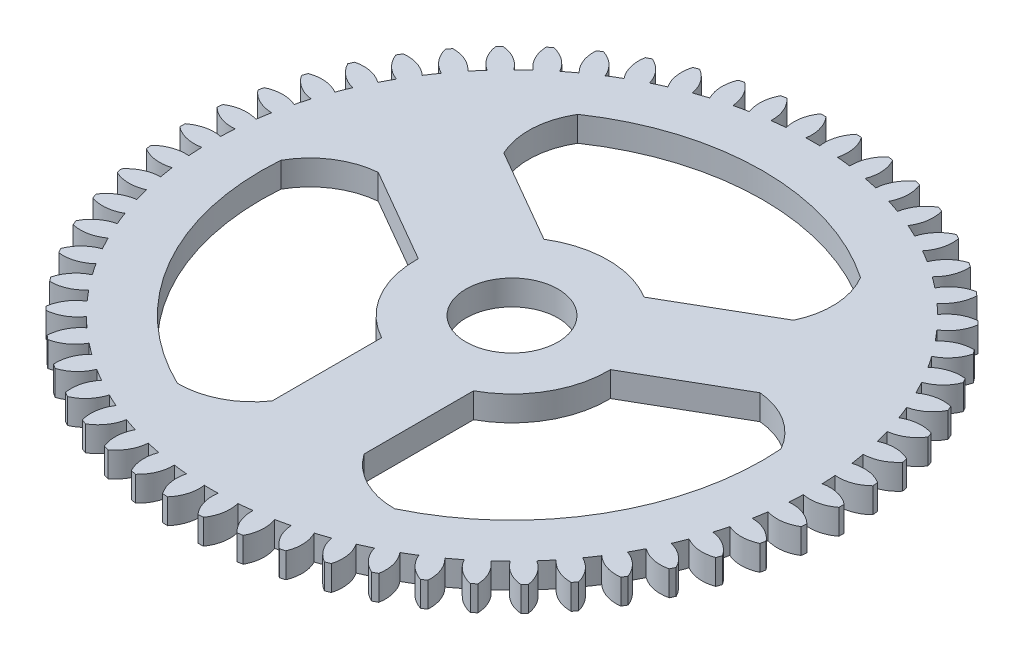
SolidWorks part; units mm, degrees
ref_plane "Front Plane" through (0, 0, 0) normal (0, 0, 1) x (1, 0, 0)
ref_plane "Top Plane" through (0, 0, 0) normal (0, 1, 0) x (1, 0, 0)
ref_plane "Right Plane" through (0, 0, 0) normal (1, 0, 0) x (0, 0, -1)
sketch "Sketch1" plane through (0, 0, 0) normal (0, 1, 0) x (1, 0, 0)
  line L0 (0, -72) -> (0, 72) construction
  line L1 (-72, 0) -> (72, 0) construction
  line L2 (50.9117, -50.9117) -> (-50.9117, 50.9117) construction
  line L3 (-50.9117, -50.9117) -> (50.9117, 50.9117) construction
  circle A58 centre (0, 0) radius 72
  arc A59 (-71.9648, 2.2507) -> (-78.8549, 0.6353) centre (-73.6708, -5.9742) ccw
  arc A60 (-78.8549, 0.6353) -> (-78.8549, -0.6353) centre (390.4055, 0) ccw
  arc A61 (-78.8549, -0.6353) -> (-71.9648, -2.2507) centre (-73.6708, 5.9742) ccw
  arc A62 (-71.9648, 2.2507) -> (-71.9648, -2.2507) centre (0, 0) ccw
  arc A63 (-71.2996, 10.0183) -> (-78.3239, 9.1572) centre (-73.8848, 2.026) ccw
  arc A64 (-78.3239, 9.1572) -> (-78.4613, 7.8942) centre (388.117, -42.2103) ccw
  arc A65 (-78.4613, 7.8942) -> (-71.7863, 5.5432) centre (-72.593, 13.9044) ccw
  arc A66 (-69.7985, 17.6684) -> (-76.8747, 17.5719) centre (-73.2327, 10.0025) ccw
  arc A67 (-76.8747, 17.5719) -> (-77.1479, 16.3311) centre (381.2781, -83.9257) ccw
  arc A68 (-77.1479, 16.3311) -> (-70.7662, 13.2722) centre (-70.6641, 21.6716) ccw
  arc A69 (-67.479, 25.1114) -> (-74.5242, 25.7805) centre (-71.7219, 17.8617) ccw
  arc A70 (-74.5242, 25.7805) -> (-74.9299, 24.5765) centre (369.9691, -124.6571) ccw
  arc A71 (-74.9299, 24.5765) -> (-68.9163, 20.8456) centre (-67.9068, 29.1847) ccw
  arc A72 (-64.3684, 32.2599) -> (-71.3, 33.6868) centre (-69.3703, 25.5115) ccw
  arc A73 (-71.3, 33.6868) -> (-71.8335, 32.5338) centre (354.3225, -163.927) ccw
  arc A74 (-71.8335, 32.5338) -> (-66.2586, 28.1745) centre (-64.3533, 36.3556) ccw
  arc A75 (-60.5032, 39.0303) -> (-67.2399, 41.1983) centre (-66.2054, 32.8622) ccw
  arc A76 (-67.2399, 41.1983) -> (-67.8949, 40.1096) centre (334.5218, -201.2751) ccw
  arc A77 (-67.8949, 40.1096) -> (-62.8239, 35.1732) centre (-60.0453, 43.1003) ccw
  arc A78 (-55.9286, 45.343) -> (-62.3914, 48.2267) centre (-62.2642, 39.8276) ccw
  arc A79 (-62.3914, 48.2267) -> (-63.1603, 47.2152) centre (310.7991, -236.2634) ccw
  arc A80 (-63.1603, 47.2152) -> (-58.6528, 41.7595) centre (-55.0333, 49.3397) ccw
  arc A81 (-50.6983, 51.1242) -> (-56.8114, 54.6896) centre (-57.5931, 46.3261) ccw
  arc A82 (-56.8114, 54.6896) -> (-57.6851, 53.7673) centre (283.4327, -268.4817) ccw
  arc A83 (-57.6851, 53.7673) -> (-53.794, 47.8561) centre (-49.3762, 55.0006) ccw
  arc A84 (-44.8736, 56.3059) -> (-50.5654, 60.5114) centre (-52.2468, 52.2814) ccw
  arc A85 (-50.5654, 60.5114) -> (-51.5337, 59.6889) centre (252.7432, -297.5523) ccw
  arc A86 (-51.5337, 59.6889) -> (-48.3045, 53.3918) centre (-43.1401, 60.0167) ccw
  arc A87 (-38.5228, 60.8276) -> (-43.7265, 65.6238) centre (-46.2879, 57.6238) ccw
  arc A88 (-43.7265, 65.6238) -> (-44.7781, 64.9108) centre (219.0905, -323.1344) ccw
  arc A89 (-44.7781, 64.9108) -> (-42.2486, 58.3014) centre (-36.3983, 64.3291) ccw
  arc A90 (-31.7204, 64.636) -> (-36.375, 69.9668) centre (-39.7863, 62.2906) ccw
  arc A91 (-36.375, 69.9668) -> (-37.4975, 69.3717) centre (182.8693, -344.928) ccw
  arc A92 (-37.4975, 69.3717) -> (-35.6975, 62.5275) centre (-29.2297, 67.8874) ccw
  arc A93 (-24.546, 67.6867) -> (-28.5971, 73.4895) centre (-32.8183, 66.2271) ccw
  arc A94 (-28.5971, 73.4895) -> (-29.7773, 73.0192) centre (144.504, -362.6777) ccw
  arc A95 (-29.7773, 73.0192) -> (-28.7278, 66.0206) centre (-21.7185, 70.6497) ccw
  arc A96 (-17.0839, 69.9438) -> (-20.4838, 76.1506) centre (-25.4655, 69.3872) ccw
  arc A97 (-20.4838, 76.1506) -> (-21.708, 75.8107) centre (104.4445, -376.1753) ccw
  arc A98 (-21.708, 75.8107) -> (-21.4213, 68.7396) centre (-13.9526, 72.5837) ccw
  arc A99 (-9.4215, 71.3809) -> (-12.1304, 77.9189) centre (-17.8141, 71.7338) ccw
  arc A100 (-12.1304, 77.9189) -> (-13.3842, 77.7133) centre (63.1606, -385.2625) ccw
  arc A101 (-13.3842, 77.7133) -> (-13.8637, 70.6527) centre (-6.0231, 73.6668) ccw
  arc A102 (-1.6487, 71.9811) -> (-3.6348, 78.7736) centre (-9.9539, 73.2393) ccw
  arc A103 (-3.6348, 78.7736) -> (-4.9034, 78.7048) centre (21.1361, -389.833) ccw
  arc A104 (-4.9034, 78.7048) -> (-6.1435, 71.7374) centre (1.977, 73.8862) ccw
  arc A105 (6.1435, 71.7374) -> (4.9034, 78.7048) centre (-1.977, 73.8862) ccw
  arc A106 (4.9034, 78.7048) -> (3.6348, 78.7736) centre (-21.1361, -389.833) ccw
  arc A107 (3.6348, 78.7736) -> (1.6487, 71.9811) centre (9.9539, 73.2393) ccw
  arc A108 (13.8637, 70.6527) -> (13.3842, 77.7133) centre (6.0231, 73.6668) ccw
  arc A109 (13.3842, 77.7133) -> (12.1304, 77.9189) centre (-63.1606, -385.2625) ccw
  arc A110 (12.1304, 77.9189) -> (9.4215, 71.3809) centre (17.8141, 71.7338) ccw
  arc A111 (21.4213, 68.7396) -> (21.708, 75.8107) centre (13.9526, 72.5837) ccw
  arc A112 (21.708, 75.8107) -> (20.4838, 76.1506) centre (-104.4445, -376.1753) ccw
  arc A113 (20.4838, 76.1506) -> (17.0839, 69.9438) centre (25.4655, 69.3872) ccw
  arc A114 (28.7278, 66.0206) -> (29.7773, 73.0192) centre (21.7185, 70.6497) ccw
  arc A115 (29.7773, 73.0192) -> (28.5971, 73.4895) centre (-144.504, -362.6777) ccw
  arc A116 (28.5971, 73.4895) -> (24.546, 67.6867) centre (32.8183, 66.2271) ccw
  arc A117 (35.6975, 62.5275) -> (37.4975, 69.3717) centre (29.2297, 67.8874) ccw
  arc A118 (37.4975, 69.3717) -> (36.375, 69.9668) centre (-182.8693, -344.928) ccw
  arc A119 (36.375, 69.9668) -> (31.7204, 64.636) centre (39.7863, 62.2906) ccw
  arc A120 (42.2486, 58.3014) -> (44.7781, 64.9108) centre (36.3983, 64.3291) ccw
  arc A121 (44.7781, 64.9108) -> (43.7265, 65.6238) centre (-219.0905, -323.1344) ccw
  arc A122 (43.7265, 65.6238) -> (38.5228, 60.8276) centre (46.2879, 57.6238) ccw
  arc A123 (48.3045, 53.3918) -> (51.5337, 59.6889) centre (43.1401, 60.0167) ccw
  arc A124 (51.5337, 59.6889) -> (50.5654, 60.5114) centre (-252.7432, -297.5523) ccw
  arc A125 (50.5654, 60.5114) -> (44.8736, 56.3059) centre (52.2468, 52.2814) ccw
  arc A126 (53.794, 47.8561) -> (57.6851, 53.7673) centre (49.3762, 55.0006) ccw
  arc A127 (57.6851, 53.7673) -> (56.8114, 54.6896) centre (-283.4327, -268.4817) ccw
  arc A128 (56.8114, 54.6896) -> (50.6983, 51.1242) centre (57.5931, 46.3261) ccw
  arc A129 (58.6528, 41.7595) -> (63.1603, 47.2152) centre (55.0333, 49.3397) ccw
  arc A130 (63.1603, 47.2152) -> (62.3914, 48.2267) centre (-310.7991, -236.2634) ccw
  arc A131 (62.3914, 48.2267) -> (55.9286, 45.343) centre (62.2642, 39.8276) ccw
  arc A132 (62.8239, 35.1732) -> (67.8949, 40.1096) centre (60.0453, 43.1003) ccw
  arc A133 (67.8949, 40.1096) -> (67.2399, 41.1983) centre (-334.5218, -201.2751) ccw
  arc A134 (67.2399, 41.1983) -> (60.5032, 39.0303) centre (66.2054, 32.8622) ccw
  arc A135 (66.2586, 28.1745) -> (71.8335, 32.5338) centre (64.3533, 36.3556) ccw
  arc A136 (71.8335, 32.5338) -> (71.3, 33.6868) centre (-354.3225, -163.927) ccw
  arc A137 (71.3, 33.6868) -> (64.3684, 32.2599) centre (69.3703, 25.5115) ccw
  arc A138 (68.9163, 20.8456) -> (74.9299, 24.5765) centre (67.9068, 29.1847) ccw
  arc A139 (74.9299, 24.5765) -> (74.5242, 25.7805) centre (-369.9691, -124.6571) ccw
  arc A140 (74.5242, 25.7805) -> (67.479, 25.1114) centre (71.7219, 17.8617) ccw
  arc A141 (70.7662, 13.2722) -> (77.1479, 16.3311) centre (70.6641, 21.6716) ccw
  arc A142 (77.1479, 16.3311) -> (76.8747, 17.5719) centre (-381.2781, -83.9257) ccw
  arc A143 (76.8747, 17.5719) -> (69.7985, 17.6684) centre (73.2327, 10.0025) ccw
  arc A144 (71.7863, 5.5432) -> (78.4613, 7.8942) centre (72.593, 13.9044) ccw
  arc A145 (78.4613, 7.8942) -> (78.3239, 9.1572) centre (-388.117, -42.2103) ccw
  arc A146 (78.3239, 9.1572) -> (71.2996, 10.0183) centre (73.8848, 2.026) ccw
  arc A147 (71.9648, -2.2507) -> (78.8549, -0.6353) centre (73.6708, 5.9742) ccw
  arc A148 (78.8549, -0.6353) -> (78.8549, 0.6353) centre (-390.4055, 0) ccw
  arc A149 (78.8549, 0.6353) -> (71.9648, 2.2507) centre (73.6708, -5.9742) ccw
  arc A150 (71.2996, -10.0183) -> (78.3239, -9.1572) centre (73.8848, -2.026) ccw
  arc A151 (78.3239, -9.1572) -> (78.4613, -7.8942) centre (-388.117, 42.2103) ccw
  arc A152 (78.4613, -7.8942) -> (71.7863, -5.5432) centre (72.593, -13.9044) ccw
  arc A153 (69.7985, -17.6684) -> (76.8747, -17.5719) centre (73.2327, -10.0025) ccw
  arc A154 (76.8747, -17.5719) -> (77.1479, -16.3311) centre (-381.2781, 83.9257) ccw
  arc A155 (77.1479, -16.3311) -> (70.7662, -13.2722) centre (70.6641, -21.6716) ccw
  arc A156 (67.479, -25.1114) -> (74.5242, -25.7805) centre (71.7219, -17.8617) ccw
  arc A157 (74.5242, -25.7805) -> (74.9299, -24.5765) centre (-369.9691, 124.6571) ccw
  arc A158 (74.9299, -24.5765) -> (68.9163, -20.8456) centre (67.9068, -29.1847) ccw
  arc A159 (64.3684, -32.2599) -> (71.3, -33.6868) centre (69.3703, -25.5115) ccw
  arc A160 (71.3, -33.6868) -> (71.8335, -32.5338) centre (-354.3225, 163.927) ccw
  arc A161 (71.8335, -32.5338) -> (66.2586, -28.1745) centre (64.3533, -36.3556) ccw
  arc A162 (60.5032, -39.0303) -> (67.2399, -41.1983) centre (66.2054, -32.8622) ccw
  arc A163 (67.2399, -41.1983) -> (67.8949, -40.1096) centre (-334.5218, 201.2751) ccw
  arc A164 (67.8949, -40.1096) -> (62.8239, -35.1732) centre (60.0453, -43.1003) ccw
  arc A165 (55.9286, -45.343) -> (62.3914, -48.2267) centre (62.2642, -39.8276) ccw
  arc A166 (62.3914, -48.2267) -> (63.1603, -47.2152) centre (-310.7991, 236.2634) ccw
  arc A167 (63.1603, -47.2152) -> (58.6528, -41.7595) centre (55.0333, -49.3397) ccw
  arc A168 (50.6983, -51.1242) -> (56.8114, -54.6896) centre (57.5931, -46.3261) ccw
  arc A169 (56.8114, -54.6896) -> (57.6851, -53.7673) centre (-283.4327, 268.4817) ccw
  arc A170 (57.6851, -53.7673) -> (53.794, -47.8561) centre (49.3762, -55.0006) ccw
  arc A171 (44.8736, -56.3059) -> (50.5654, -60.5114) centre (52.2468, -52.2814) ccw
  arc A172 (50.5654, -60.5114) -> (51.5337, -59.6889) centre (-252.7432, 297.5523) ccw
  arc A173 (51.5337, -59.6889) -> (48.3045, -53.3918) centre (43.1401, -60.0167) ccw
  arc A174 (38.5228, -60.8276) -> (43.7265, -65.6238) centre (46.2879, -57.6238) ccw
  arc A175 (43.7265, -65.6238) -> (44.7781, -64.9108) centre (-219.0905, 323.1344) ccw
  arc A176 (44.7781, -64.9108) -> (42.2486, -58.3014) centre (36.3983, -64.3291) ccw
  arc A177 (31.7204, -64.636) -> (36.375, -69.9668) centre (39.7863, -62.2906) ccw
  arc A178 (36.375, -69.9668) -> (37.4975, -69.3717) centre (-182.8693, 344.928) ccw
  arc A179 (37.4975, -69.3717) -> (35.6975, -62.5275) centre (29.2297, -67.8874) ccw
  arc A180 (24.546, -67.6867) -> (28.5971, -73.4895) centre (32.8183, -66.2271) ccw
  arc A181 (28.5971, -73.4895) -> (29.7773, -73.0192) centre (-144.504, 362.6777) ccw
  arc A182 (29.7773, -73.0192) -> (28.7278, -66.0206) centre (21.7185, -70.6497) ccw
  arc A183 (17.0839, -69.9438) -> (20.4838, -76.1506) centre (25.4655, -69.3872) ccw
  arc A184 (20.4838, -76.1506) -> (21.708, -75.8107) centre (-104.4445, 376.1753) ccw
  arc A185 (21.708, -75.8107) -> (21.4213, -68.7396) centre (13.9526, -72.5837) ccw
  arc A186 (9.4215, -71.3809) -> (12.1304, -77.9189) centre (17.8141, -71.7338) ccw
  arc A187 (12.1304, -77.9189) -> (13.3842, -77.7133) centre (-63.1606, 385.2625) ccw
  arc A188 (13.3842, -77.7133) -> (13.8637, -70.6527) centre (6.0231, -73.6668) ccw
  arc A189 (1.6487, -71.9811) -> (3.6348, -78.7736) centre (9.9539, -73.2393) ccw
  arc A190 (3.6348, -78.7736) -> (4.9034, -78.7048) centre (-21.1361, 389.833) ccw
  arc A191 (4.9034, -78.7048) -> (6.1435, -71.7374) centre (-1.977, -73.8862) ccw
  arc A192 (-6.1435, -71.7374) -> (-4.9034, -78.7048) centre (1.977, -73.8862) ccw
  arc A193 (-4.9034, -78.7048) -> (-3.6348, -78.7736) centre (21.1361, 389.833) ccw
  arc A194 (-3.6348, -78.7736) -> (-1.6487, -71.9811) centre (-9.9539, -73.2393) ccw
  arc A195 (-13.8637, -70.6527) -> (-13.3842, -77.7133) centre (-6.0231, -73.6668) ccw
  arc A196 (-13.3842, -77.7133) -> (-12.1304, -77.9189) centre (63.1606, 385.2625) ccw
  arc A197 (-12.1304, -77.9189) -> (-9.4215, -71.3809) centre (-17.8141, -71.7338) ccw
  arc A198 (-21.4213, -68.7396) -> (-21.708, -75.8107) centre (-13.9526, -72.5837) ccw
  arc A199 (-21.708, -75.8107) -> (-20.4838, -76.1506) centre (104.4445, 376.1753) ccw
  arc A200 (-20.4838, -76.1506) -> (-17.0839, -69.9438) centre (-25.4655, -69.3872) ccw
  arc A201 (-28.7278, -66.0206) -> (-29.7773, -73.0192) centre (-21.7185, -70.6497) ccw
  arc A202 (-29.7773, -73.0192) -> (-28.5971, -73.4895) centre (144.504, 362.6777) ccw
  arc A203 (-28.5971, -73.4895) -> (-24.546, -67.6867) centre (-32.8183, -66.2271) ccw
  arc A204 (-35.6975, -62.5275) -> (-37.4975, -69.3717) centre (-29.2297, -67.8874) ccw
  arc A205 (-37.4975, -69.3717) -> (-36.375, -69.9668) centre (182.8693, 344.928) ccw
  arc A206 (-36.375, -69.9668) -> (-31.7204, -64.636) centre (-39.7863, -62.2906) ccw
  arc A207 (-42.2486, -58.3014) -> (-44.7781, -64.9108) centre (-36.3983, -64.3291) ccw
  arc A208 (-44.7781, -64.9108) -> (-43.7265, -65.6238) centre (219.0905, 323.1344) ccw
  arc A209 (-43.7265, -65.6238) -> (-38.5228, -60.8276) centre (-46.2879, -57.6238) ccw
  arc A210 (-48.3045, -53.3918) -> (-51.5337, -59.6889) centre (-43.1401, -60.0167) ccw
  arc A211 (-51.5337, -59.6889) -> (-50.5654, -60.5114) centre (252.7432, 297.5523) ccw
  arc A212 (-50.5654, -60.5114) -> (-44.8736, -56.3059) centre (-52.2468, -52.2814) ccw
  arc A213 (-53.794, -47.8561) -> (-57.6851, -53.7673) centre (-49.3762, -55.0006) ccw
  arc A214 (-57.6851, -53.7673) -> (-56.8114, -54.6896) centre (283.4327, 268.4817) ccw
  arc A215 (-56.8114, -54.6896) -> (-50.6983, -51.1242) centre (-57.5931, -46.3261) ccw
  arc A216 (-58.6528, -41.7595) -> (-63.1603, -47.2152) centre (-55.0333, -49.3397) ccw
  arc A217 (-63.1603, -47.2152) -> (-62.3914, -48.2267) centre (310.7991, 236.2634) ccw
  arc A218 (-62.3914, -48.2267) -> (-55.9286, -45.343) centre (-62.2642, -39.8276) ccw
  arc A219 (-62.8239, -35.1732) -> (-67.8949, -40.1096) centre (-60.0453, -43.1003) ccw
  arc A220 (-67.8949, -40.1096) -> (-67.2399, -41.1983) centre (334.5218, 201.2751) ccw
  arc A221 (-67.2399, -41.1983) -> (-60.5032, -39.0303) centre (-66.2054, -32.8622) ccw
  arc A222 (-66.2586, -28.1745) -> (-71.8335, -32.5338) centre (-64.3533, -36.3556) ccw
  arc A223 (-71.8335, -32.5338) -> (-71.3, -33.6868) centre (354.3225, 163.927) ccw
  arc A224 (-71.3, -33.6868) -> (-64.3684, -32.2599) centre (-69.3703, -25.5115) ccw
  arc A225 (-68.9163, -20.8456) -> (-74.9299, -24.5765) centre (-67.9068, -29.1847) ccw
  arc A226 (-74.9299, -24.5765) -> (-74.5242, -25.7805) centre (369.9691, 124.6571) ccw
  arc A227 (-74.5242, -25.7805) -> (-67.479, -25.1114) centre (-71.7219, -17.8617) ccw
  arc A228 (-70.7662, -13.2722) -> (-77.1479, -16.3311) centre (-70.6641, -21.6716) ccw
  arc A229 (-77.1479, -16.3311) -> (-76.8747, -17.5719) centre (381.2781, 83.9257) ccw
  arc A230 (-76.8747, -17.5719) -> (-69.7985, -17.6684) centre (-73.2327, -10.0025) ccw
  arc A231 (-71.7863, -5.5432) -> (-78.4613, -7.8942) centre (-72.593, -13.9044) ccw
  arc A232 (-78.4613, -7.8942) -> (-78.3239, -9.1572) centre (388.117, 42.2103) ccw
  arc A233 (-78.3239, -9.1572) -> (-71.2996, -10.0183) centre (-73.8848, -2.026) ccw
  circle A234 centre (0, 0) radius 11
  point P5 (0, 0)
  point P7 (0, 0)
  point P9 (-72, 0)
  point P10 (859.6664, 0)
  point P18 (0, 0)
  point P21 (0, 0)
  point P26 (0, 0)
  point P27 (0, 0)
  point P427 (0, 0)
  point P428 (0, 0)
  dimension "D1" = 144
  dimension "D2" = 45
  dimension "D3" = 45
  dimension "D4" = 8.4
  dimension "D5" = 1.2705
  dimension "D9" = 72
  dimension "D10" = 469.2609
  dimension "D12" = 22
  dimension "D6" = 6.8901
  dimension "D7" = 6.8901
  dimension "D8" = 4.5015
  dimension "D11" = 58
extrude "Boss-Extrude5" add sketch "Sketch1" along normal blind 6 contours A58 region at (69.955, 0, 1.0937)
extrude "Boss-Extrude6" add sketch "Sketch1<10>" along normal blind 6 contours A60 A61 A58 A59 region at (-74.9733, 0, 0)
sketch "Sketch1<10>" plane through (0, 0, 0) normal (0, 1, 0) x (1, 0, 0) same geometry as "Sketch1"
pattern_circular "CirPattern1" count 58 over 360 about axis through (0, 6, 0) along (0, 1, 0) of "Boss-Extrude6"
sketch "Sketch3" plane through (0, 6, 0) normal (0, 1, 0) x (1, 0, 0)
  line L1 (11.9929, 19.6258) -> (34.6743, 32.721)
  line L2 (0, -11) -> (0, -60) construction
  line L4 (-22.9929, 0.5732) -> (-45.6743, 13.6684)
  line L5 (-11, -20.199) -> (-11, -46.3893)
  line L6 (-11.9929, 19.6258) -> (-34.6743, 32.721)
  line L7 (22.9929, 0.5732) -> (45.6743, 13.6684)
  line L8 (11, -20.199) -> (11, -46.3893)
  arc A0 (13.8878, -70.6479) -> (-13.8878, -70.6479) centre (0, 0) ccw
  circle A1 centre (0, 0) radius 11 construction
  circle A2 centre (0, 0) radius 11
  circle A3 centre (0, 0) radius 60
  arc A5 (-26, -54.074) -> (-11, -46.3893) centre (-25.7523, -36.0757) ccw
  arc A6 (26, -54.074) -> (11, -46.3893) centre (25.7523, -36.0757) cw
  arc A7 (-59.8295, 4.5204) -> (-45.6743, 13.6684) centre (-44.1186, -4.2643) cw
  arc A8 (-33.8295, 49.5537) -> (-34.6743, 32.721) centre (-18.3664, 40.34) ccw
  arc A9 (33.8295, 49.5537) -> (34.6743, 32.721) centre (18.3664, 40.34) cw
  arc A10 (59.8295, 4.5204) -> (45.6743, 13.6684) centre (44.1186, -4.2643) ccw
  circle A11 centre (0, 0) radius 23
  point P9 (0, 0)
  point P11 (0, 0)
  point P26 (0, 0)
  point P34 (0, 0)
  point P39 (0, 0)
  point P41 (0, 0)
  point P42 (0, 0)
  point P43 (0, 0)
  dimension "D1" = 12
  dimension "D2" = 18
  dimension "D3" = 15
  dimension "D6" = 12
  dimension "D4" = 46.3893
  dimension "D7" = 11
  dimension "D8" = 20.199
  dimension "D9" = 22
  dimension "D10" = 22
  dimension "D5" = 3
extrude "Cut-Extrude1" cut sketch "Sketch3" against normal blind 6 contours A11 L1 A9 A3 A8 L6 | A11 L4 A7 A3 A5 L5 | A11 L8 A6 A3 A10 L7 region at (0, 6, -40.5259) region at (35.0964, 6, 20.2629) region at (-35.0964, 6, 20.2629)
